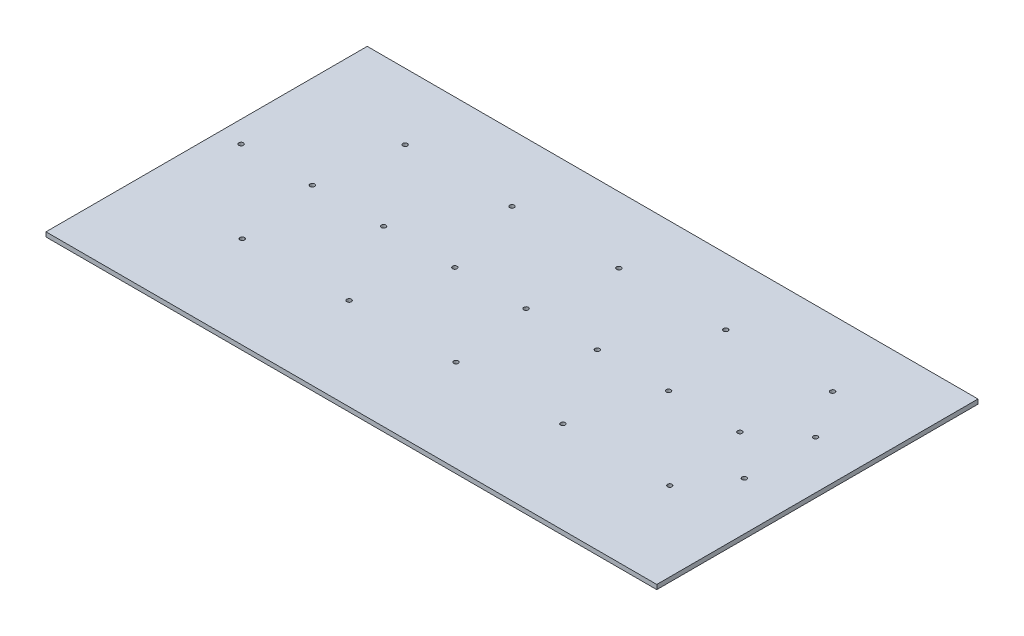
SolidWorks part; units mm, degrees
ref_plane "Front Plane" through (0, 0, 0) normal (0, 0, 1) x (1, 0, 0)
ref_plane "Top Plane" through (0, 0, 0) normal (0, 1, 0) x (1, 0, 0)
ref_plane "Right Plane" through (0, 0, 0) normal (1, 0, 0) x (0, 0, -1)
sketch "Sketch1" plane through (0, 0, 0) normal (0, 1, 0) x (1, 0, 0)
  line L1 (0, 0) -> (857.25, 0)
  line L2 (0, 0) -> (0, 450.85)
  line L3 (0, 450.85) -> (857.25, 450.85)
  line L4 (857.25, 0) -> (857.25, 450.85)
  dimension "D1" = 450.85
  dimension "D2" = 857.25
extrude "Boss-Extrude1" add sketch "Sketch1" along normal blind 6.35
sketch "Sketch2" plane through (0, 6.35, 0) normal (0, 1, 0) x (1, 0, 0)
  line L0 (30.25, 243.5678) -> (0, 243.5678) construction
  line L1 (0, 450.85) -> (0, 0) construction
  line L2 (730.25, 243.5678) -> (857.25, 243.5678) construction
  line L3 (30.25, 243.5678) -> (130.25, 243.5678) construction
  line L4 (146.163, 357.8678) -> (0, 357.8678) construction
  line L5 (857.25, 0) -> (857.25, 450.85) construction
  line L6 (130.25, 243.5678) -> (230.25, 243.5678) construction
  line L7 (230.25, 243.5678) -> (330.25, 243.5678) construction
  line L8 (330.25, 243.5678) -> (430.25, 243.5678) construction
  line L9 (430.25, 243.5678) -> (530.25, 243.5678) construction
  line L10 (530.25, 243.5678) -> (630.25, 243.5678) construction
  line L11 (630.25, 243.5678) -> (730.25, 243.5678) construction
  line L12 (146.163, 357.8678) -> (296.163, 357.8678) construction
  line L13 (296.163, 357.8678) -> (446.163, 357.8678) construction
  line L14 (446.163, 357.8678) -> (596.163, 357.8678) construction
  line L15 (596.163, 357.8678) -> (746.163, 357.8678) construction
  line L16 (746.163, 357.8678) -> (857.25, 357.8678) construction
  line L17 (146.163, 129.2678) -> (0, 129.2678) construction
  line L18 (146.163, 129.2678) -> (296.163, 129.2678) construction
  line L19 (296.163, 129.2678) -> (296.1632, 129.0266) construction
  line L20 (296.1632, 129.0266) -> (446.163, 129.2678) construction
  line L21 (446.163, 129.2678) -> (596.163, 129.2678) construction
  line L22 (596.163, 129.2678) -> (746.163, 129.2678) construction
  line L23 (746.163, 129.2678) -> (857.25, 129.2678) construction
  line L24 (789.663, 190.4666) -> (789.663, 129.2678) construction
  line L25 (789.663, 190.4666) -> (789.663, 290.4664) construction
  circle A0 centre (30.25, 243.5678) radius 3.175
  circle A2 centre (130.25, 243.5678) radius 3.175
  circle A3 centre (230.25, 243.5678) radius 3.175
  circle A4 centre (330.25, 243.5678) radius 3.175
  circle A5 centre (430.25, 243.5678) radius 3.175
  circle A6 centre (530.25, 243.5678) radius 3.175
  circle A7 centre (630.25, 243.5678) radius 3.175
  circle A8 centre (730.25, 243.5678) radius 3.175
  circle A11 centre (146.163, 357.8678) radius 3.175
  circle A12 centre (296.163, 357.8678) radius 3.175
  circle A13 centre (446.163, 357.8678) radius 3.175
  circle A14 centre (596.163, 357.8678) radius 3.175
  circle A15 centre (746.163, 357.8678) radius 3.175
  circle A16 centre (146.163, 129.2678) radius 3.175
  circle A17 centre (296.163, 129.2678) radius 3.175
  circle A18 centre (446.163, 129.2678) radius 3.175
  circle A19 centre (596.163, 129.2678) radius 3.175
  circle A20 centre (746.163, 129.2678) radius 3.175
  circle A21 centre (789.663, 190.4666) radius 3.175
  circle A22 centre (789.663, 290.4664) radius 3.175
  dimension "D1" = 6.35
  dimension "D4" = 150
  dimension "D11" = 43.5
  dimension "D2" = 100
  dimension "D3" = 114.3
  dimension "D5" = 111.087
  dimension "D6" = 114.3
  dimension "D7" = 150
  dimension "D8" = 127
  dimension "D9" = 61.1988
  dimension "D10" = 99.9998
extrude "Cut-Extrude1" cut sketch "Sketch2" against normal through all both and the other way through all
